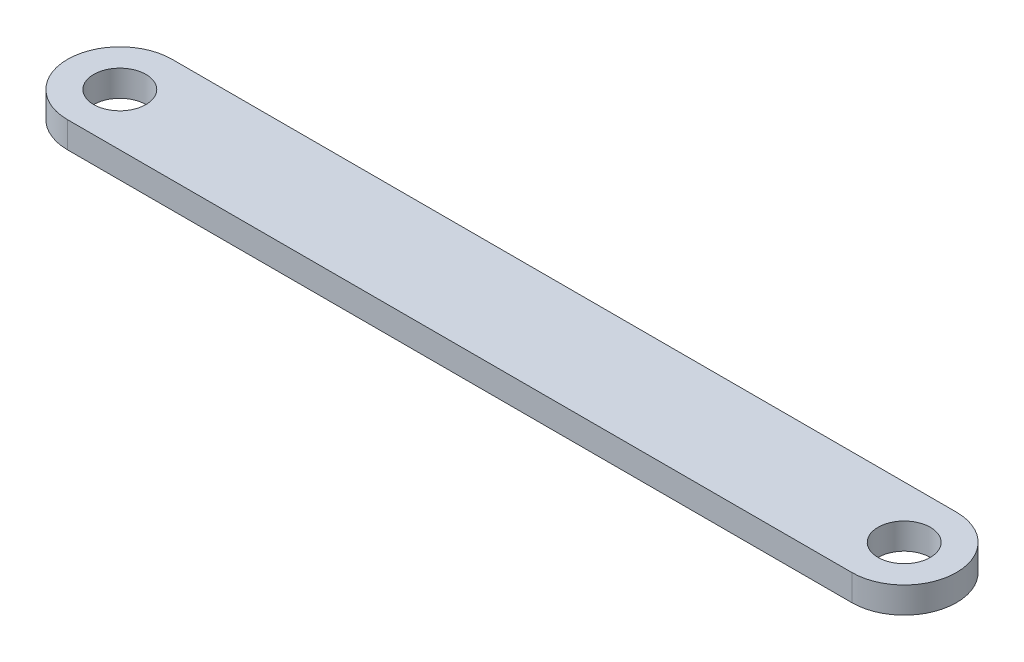
SolidWorks part; units mm, degrees
ref_plane "Ön Düzlem" through (0, 0, 0) normal (0, 0, 1) x (1, 0, 0)
ref_plane "Üst Düzlem" through (0, 0, 0) normal (0, 1, 0) x (1, 0, 0)
ref_plane "Sağ Düzlem" through (0, 0, 0) normal (1, 0, 0) x (0, 0, -1)
sketch "Sketch1" plane through (0, 0, 0) normal (0, 1, 0) x (1, 0, 0)
  line L0 (-75, 0) -> (75, 0) construction
  line L1 (-75, 10) -> (75, 10)
  line L2 (-75, -10) -> (75, -10)
  arc A0 (-75, 10) -> (-75, -10) centre (-75, 0) ccw
  arc A1 (75, -10) -> (75, 10) centre (75, 0) ccw
  circle A2 centre (-75, 0) radius 5
  circle A3 centre (75, 0) radius 5
  point P2 (0, 0)
  dimension "D1" = 10
  dimension "D3" = 10
  dimension "D4" = 10
  dimension "D2" = 150
extrude "Boss-Extrude1" add sketch "Sketch1" along normal blind 5
